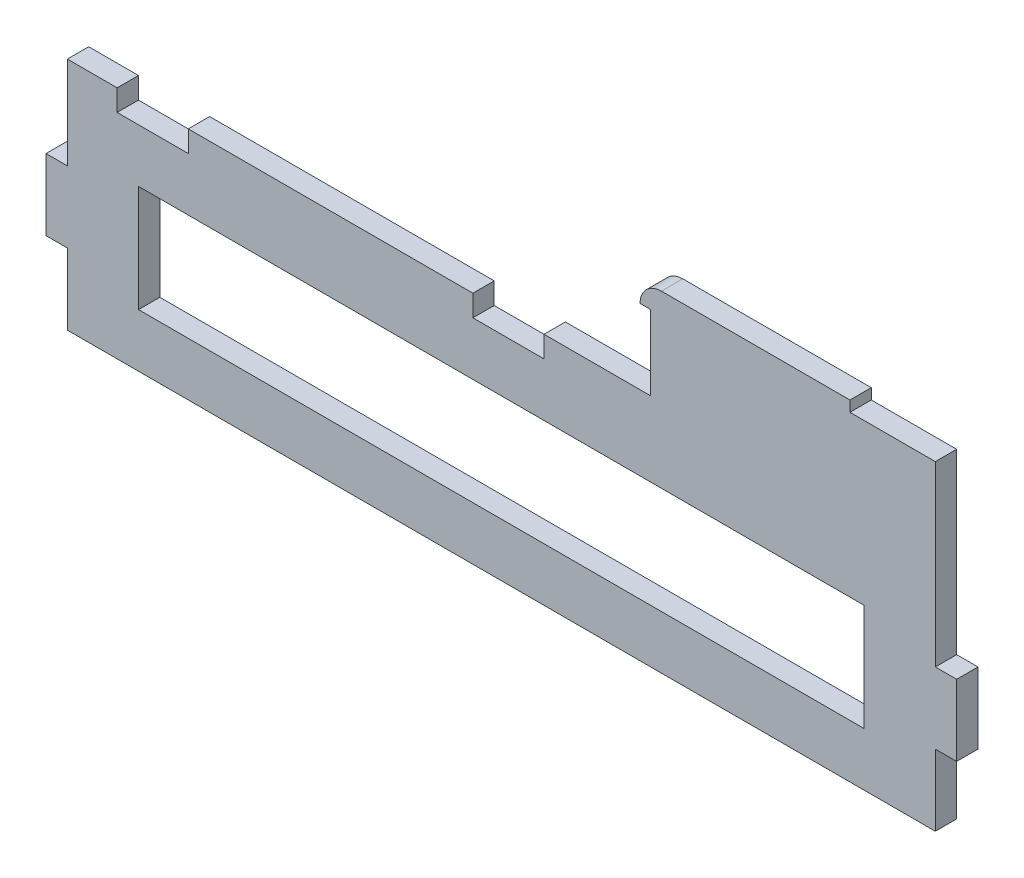
SolidWorks part; units mm, degrees
ref_plane "Спереди" through (0, 0, 0) normal (0, 0, 1) x (1, 0, 0)
ref_plane "Сверху" through (0, 0, 0) normal (0, 1, 0) x (1, 0, 0)
ref_plane "Справа" through (0, 0, 0) normal (1, 0, 0) x (0, 0, -1)
sketch "Эскиз1" plane through (0, 0, 0) normal (0, 0, 1) x (1, 0, 0)
  line L0 (0, 20) -> (0, 0)
  line L1 (0, 0) -> (244, 0)
  line L3 (0, 66) -> (154, 66) construction
  line L4 (244, 0) -> (244, 54) construction
  line L5 (244, 40) -> (250, 40)
  line L7 (244, 20) -> (250, 20)
  line L8 (250, 40) -> (250, 20)
  line L9 (0, 40) -> (-6, 40)
  line L11 (0, 20) -> (-6, 20)
  line L12 (-6, 40) -> (-6, 20)
  line L13 (0, 66) -> (0, 40)
  line L14 (0, 54) -> (0, 0) construction
  line L15 (244, 0) -> (244, 20)
  line L19 (164, 87) -> (164, 66)
  line L24 (164, 66) -> (134, 66)
  line L25 (134, 66) -> (134, 60)
  line L26 (134, 60) -> (114, 60)
  line L27 (114, 60) -> (114, 66)
  line L28 (114, 66) -> (34, 66)
  line L29 (34, 66) -> (34, 60)
  line L30 (34, 60) -> (14, 60)
  line L31 (14, 60) -> (14, 66)
  line L32 (14, 66) -> (0, 66)
  line L35 (244, 90) -> (244, 40)
  line L36 (20, 15) -> (224, 15)
  line L37 (20, 15) -> (20, 45)
  line L38 (20, 45) -> (224, 45)
  line L39 (224, 15) -> (224, 45)
  line L40 (161, 93) -> (220, 93)
  line L43 (164, 87) -> (161, 87)
  line L44 (161, 93) -> (161, 87)
  line L45 (220, 93) -> (220, 90)
  line L46 (220, 90) -> (244, 90)
  dimension "D1" = 244
  dimension "D2" = 66
  dimension "D3" = 20
  dimension "D4" = 20
  dimension "D5" = 6
  dimension "D6" = 6
  dimension "D7" = 20
  dimension "D8" = 20
  dimension "D9" = 53
  dimension "D10" = 24
  dimension "D11" = 21
  dimension "D12" = 14
  dimension "D13" = 20
  dimension "D14" = 6
  dimension "D15" = 6
  dimension "D16" = 80
  dimension "D17" = 20
  dimension "D18" = 20
  dimension "D19" = 3
  dimension "D20" = 15
  dimension "D21" = 6
  dimension "D22" = 3
  dimension "D23" = 59
extrude "Бобышка-Вытянуть1" add sketch "Эскиз1" along normal blind 6
fillet "Скругление2" radius 6 1 edges at (161, 93, 3) type face fillet first side face at (161, 90, 3) second side face at (190.5, 93, 3)
